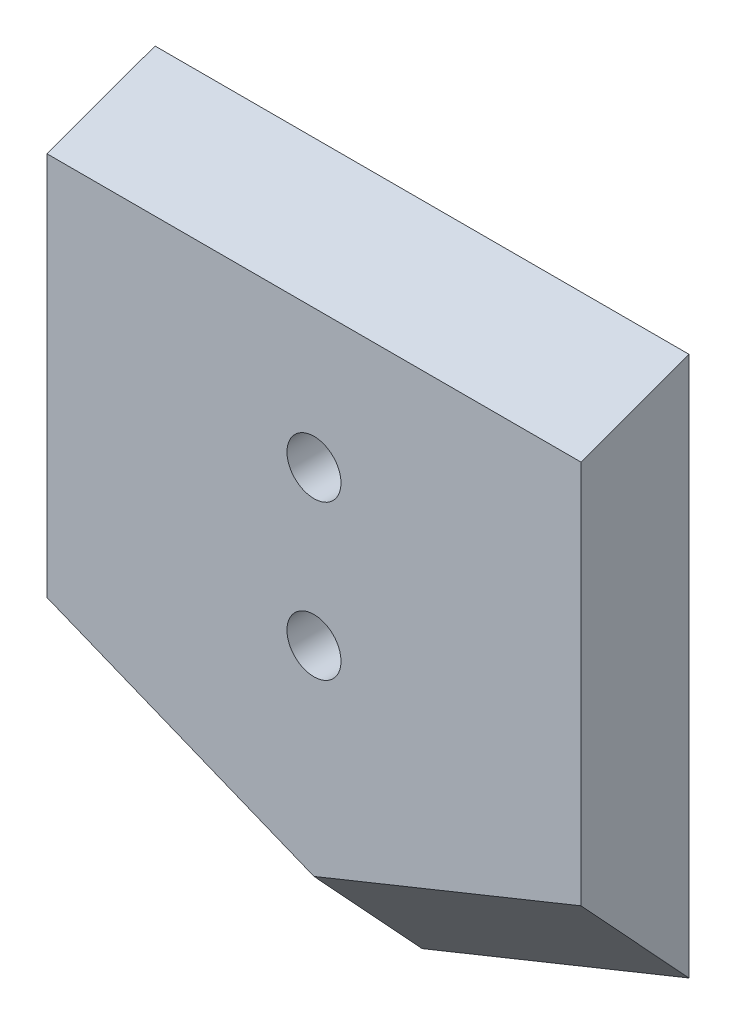
SolidWorks part; units mm, degrees
ref_plane "Plano frontal" through (0, 0, 0) normal (0, 0, 1) x (1, 0, 0)
ref_plane "Plano superior" through (0, 0, 0) normal (0, 1, 0) x (1, 0, 0)
ref_plane "Plano direito" through (0, 0, 0) normal (1, 0, 0) x (0, 0, -1)
sketch "Esboço1" plane through (0, 0, 0) normal (0, 0, 1) x (1, 0, 0)
  line L1 (-17.3, 13) -> (17.3, 13)
  line L2 (-17.3, 13) -> (-17.3, -13)
  line L3 (-17.3, -13) -> (17.3, -13)
  line L4 (17.3, 13) -> (17.3, -13)
  line L5 (-17.3, 13) -> (17.3, -13) construction
  line L6 (-17.3, -13) -> (17.3, 13) construction
  point P0 (0, 0)
  dimension "D1" = 34.6
  dimension "D2" = 26
extrude "Ressalto-extrusão1" add sketch "Esboço1" along normal blind 7
sketch "Esboço10" plane through (0, 0, 0) normal (0, 0, -1) x (-1, 0, 0)
  line L0 (-17.3, -19.5) -> (0, -26.5)
  line L1 (-17.3, 13) -> (17.3, 13)
  line L2 (-17.3, 13) -> (-17.3, 15.5)
  line L3 (-17.3, 15.5) -> (17.3, 15.5)
  line L4 (17.3, 13) -> (17.3, 15.5)
  line L5 (0, -26.5) -> (17.3, -19.5)
  line L6 (-17.3, -19.5) -> (-17.3, -13)
  line L7 (-17.3, -13) -> (17.3, -13)
  line L8 (17.3, -13) -> (17.3, -19.5)
  dimension "D1" = 7
  dimension "D2" = 35
  dimension "D3" = 2.5
extrude "Ressalto-extrusão4" add sketch "Esboço10" against normal up to surface (7 mm away) up to face at (0, 0, 7)
chamfer "Chanfro1" distance 7 angle 45 2 edges at (8.65, -23, 7) (-8.65, -23, 7)
chamfer "Chanfro2" distance 7 angle 20 1 edges at (0, 15.5, 7) first distance on face at (0, 15.5, 3.5)
sketch "Esboço11" plane through (0, 0, 7) normal (0, 0, 1) x (1, 0, 0)
  line L0 (0, 9.9803) -> (0, 0) construction
  circle A2 centre (0, -6) radius 1.75
  circle A3 centre (0, 4) radius 1.75
  point P0 (0, 0)
  dimension "D1" = 10
  dimension "D2" = 3.5
  dimension "D3" = 4
extrude "Corte-extrusão1" cut sketch "Esboço11" against normal through all
sketch "Esboço12" plane through (0, 0, 0) normal (0, 0, -1) x (-1, 0, 0)
  circle A1 centre (0, 4) radius 3.5
  circle A3 centre (0, -6) radius 3.5
  dimension "D1" = 7
extrude "Corte-extrusão2" cut sketch "Esboço12" against normal blind 3
